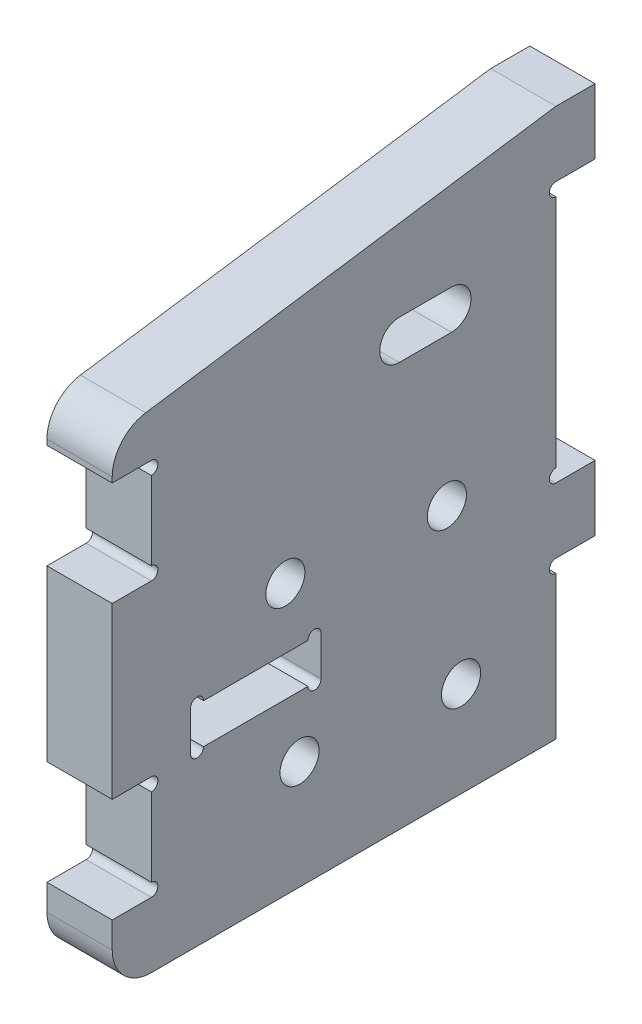
SolidWorks part; units mm, degrees
ref_plane "Front Plane" through (0, 0, 0) normal (0, 0, 1) x (1, 0, 0)
ref_plane "Top Plane" through (0, 0, 0) normal (0, 1, 0) x (1, 0, 0)
ref_plane "Right Plane" through (0, 0, 0) normal (1, 0, 0) x (0, 0, -1)
sketch "Sketch1" plane through (0, 0, 0) normal (1, 0, 0) x (0, 0, -1)
  line L0 (17, 28) -> (17, 23)
  line L1 (17, 28) -> (14, 28)
  line L2 (14, 28) -> (-20, 23)
  line L3 (-20, 23) -> (-20, -14)
  line L4 (14, -14) -> (-20, -14)
  line L6 (17, 23) -> (14, 23)
  line L7 (14, 23) -> (14, 3)
  line L8 (14, 3) -> (17, 3)
  line L9 (17, 3) -> (17, -2)
  line L10 (17, -2) -> (14, -2)
  line L11 (-6.7339, 6.7011) -> (6.7339, -6.7011) construction
  line L12 (20, 36.7745) -> (20, -39.1651) construction
  line L13 (5.643, 5.6706) -> (-5.643, -5.6706) construction
  line L14 (14, -2) -> (14, -14)
  circle A0 centre (0, 0) radius 18 construction
  circle A1 centre (-6.7339, 6.7011) radius 1.5
  circle A2 centre (-5.643, -5.6706) radius 1.5
  circle A3 centre (6.7339, -6.7011) radius 1.5
  circle A4 centre (5.643, 5.6706) radius 1.5
  dimension "D2" = 36
  dimension "D4" = 3
  dimension "D1" = 20
  dimension "D3" = 13.4022
  dimension "D5" = 5
  dimension "D6" = 3
  dimension "D7" = 17
  dimension "D8" = 14
  dimension "D9" = 12
  dimension "D10" = 28
  dimension "D11" = 20
  dimension "D12" = 5
  dimension "D13" = 5.643
  dimension "D14" = 6.7339
extrude "Boss-Extrude1" add sketch "Sketch1" along normal blind 5
sketch "Sketch2" plane through (5, 0, 0) normal (1, 0, 0) x (0, 0, -1)
  line L0 (-20, 20) -> (-17, 20)
  line L1 (-14, 2.05) -> (-4, 2.05)
  line L2 (-14, 2.05) -> (-14, -1)
  line L3 (-14, -1) -> (-4, -1)
  line L4 (-4, 2.05) -> (-4, -1)
  line L5 (-20, -14) -> (14, -14) construction
  line L7 (-20, 23) -> (-20, -14) construction
  line L8 (-17, 20) -> (-17, 12)
  line L9 (-17, -9) -> (-20, -9)
  line L10 (-17, 12) -> (-20, 12)
  line L11 (-17, -9) -> (-17, -1)
  line L12 (-17, -1) -> (-20, -1)
  line L13 (-20, 20) -> (-20, 12)
  line L14 (-20, -1) -> (-20, -9)
  dimension "D3" = 10
  dimension "D1" = 3.05
  dimension "D2" = 13
  dimension "D4" = 4
  dimension "D5" = 3
  dimension "D6" = 8
  dimension "D7" = 8
  dimension "D8" = 13
  dimension "D9" = 5
extrude "Cut-Extrude1" cut sketch "Sketch2" against normal through all
sketch "Sketch3" plane through (5, 0, 0) normal (1, 0, 0) x (0, 0, -1)
  line L0 (14, 3) -> (14, 23) construction
  line L1 (14, -14) -> (14, -2) construction
  line L2 (-4, 2.05) -> (-14, 2.05) construction
  line L3 (-14, -1) -> (-4, -1) construction
  line L4 (-17, -9) -> (-17, -1) construction
  line L5 (-17, 12) -> (-17, 20) construction
  arc A0 (14, 23) -> (14, 22) centre (14, 22.5) ccw
  arc A1 (14, 3) -> (14, 4) centre (14, 3.5) cw
  arc A2 (14, -2) -> (14, -3) centre (14, -2.5) ccw
  arc A3 (-4, 2.05) -> (-5, 2.05) centre (-4.5, 2.05) ccw
  arc A4 (-14, 2.05) -> (-13, 2.05) centre (-13.5, 2.05) cw
  arc A5 (-14, -1) -> (-13, -1) centre (-13.5, -1) ccw
  arc A6 (-4, -1) -> (-5, -1) centre (-4.5, -1) cw
  arc A7 (-17, -1) -> (-17, -2) centre (-17, -1.5) cw
  arc A8 (-17, -9) -> (-17, -8) centre (-17, -8.5) ccw
  arc A9 (-17, 20) -> (-17, 19) centre (-17, 19.5) cw
  arc A10 (-17, 12) -> (-17, 13) centre (-17, 12.5) ccw
  line M2 (-14, 2.05) -> (-4, 2.05)
  line M4 (-4, -1) -> (-14, -1)
  line M10 (14, -14) -> (14, -2)
  line M14 (14, 3) -> (14, 23)
  line M43 (-17, 20) -> (-17, 12)
  line M47 (-17, -1) -> (-17, -9)
  dimension "D1" = 0.5
extrude "Cut-Extrude2" cut sketch "Sketch3" against normal through all contours A4 M2 | A5 M4 | A3 M2 | A6 M4 | A1 M14 | A2 M10 | A0 M14 | A9 M43 | A10 M43 | A7 M47 | A8 M47 region at (5, 22.5, -13.7878) region at (5, 3.5, -13.7878) region at (5, -2.5, -13.7878) region at (5, 2.2622, 4.5) region at (5, 2.2622, 13.5) region at (5, -1.2122, 13.5) region at (5, -1.2122, 4.5) region at (5, -8.5, 16.7878) region at (5, -1.5, 16.7878) region at (5, 12.5, 16.7878) region at (5, 19.5, 16.7878)
sketch "Sketch4" plane through (5, 0, 0) normal (1, 0, 0) x (0, 0, -1)
  line L0 (2, 20) -> (6, 20)
  line L1 (2, 17) -> (6, 17)
  line L2 (17, 28) -> (14, 28) construction
  line L3 (14, 4) -> (14, 22) construction
  arc A0 (2, 20) -> (2, 17) centre (2, 18.5) ccw
  arc A1 (6, 20) -> (6, 17) centre (6, 18.5) cw
  dimension "D1" = 1.5
  dimension "D4" = 8
  dimension "D2" = 4
  dimension "D3" = 8
extrude "Cut-Extrude3" cut sketch "Sketch4" against normal blind 10
fillet "Fillet1" radius 3 2 edges at (2.5, 23, 20) (2.5, -14, 20)
